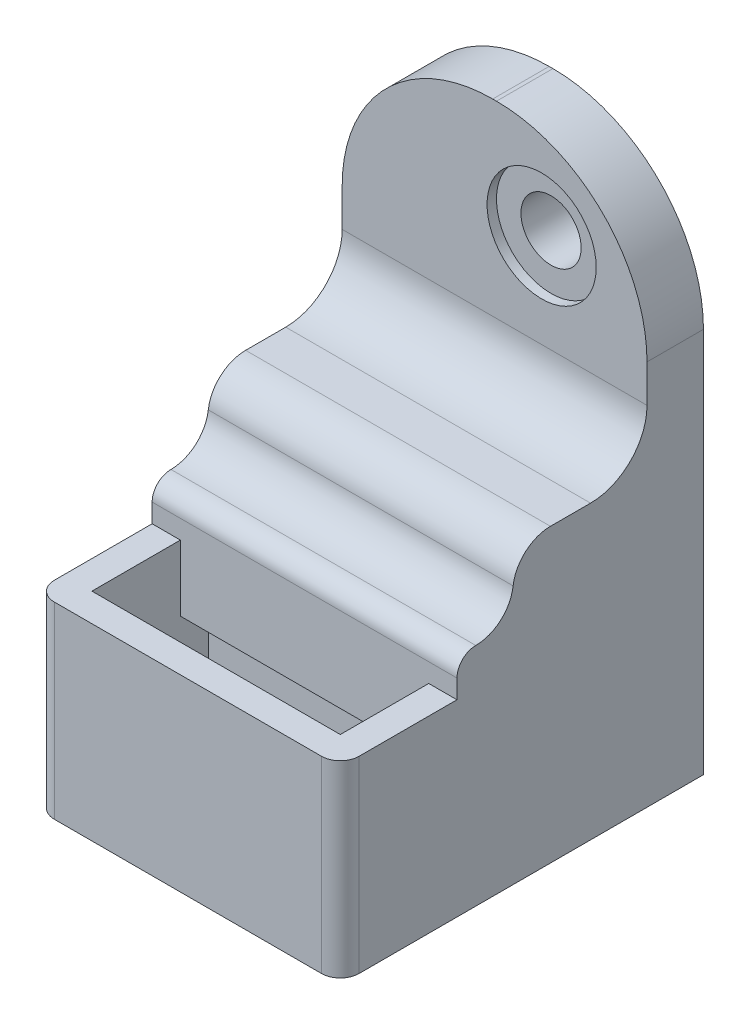
SolidWorks part; units mm, degrees
ref_plane "Alzado" through (0, 0, 0) normal (0, 0, 1) x (1, 0, 0)
ref_plane "Planta" through (0, 0, 0) normal (0, 1, 0) x (1, 0, 0)
ref_plane "Vista lateral" through (0, 0, 0) normal (1, 0, 0) x (0, 0, -1)
sketch "Croquis2" plane through (0, 0, 0) normal (0, 1, 0) x (1, 0, 0)
  line L0 (-1.5, 1.5) -> (14.7, 1.5)
  line L1 (0, 0) -> (13.2, 0)
  line L2 (0, 0) -> (0, -6.2)
  line L3 (0, -6.2) -> (13.2, -6.2)
  line L4 (13.2, 0) -> (13.2, -6.2)
  line L5 (14.7, 1.5) -> (14.7, -7.7)
  line L6 (-1.5, -7.7) -> (14.7, -7.7)
  line L7 (-1.5, 1.5) -> (-1.5, -7.7)
  dimension "D1" = 13.2
  dimension "D2" = 6.2
  dimension "D3" = 1.5
extrude "Saliente-Extruir1" add sketch "Croquis2" along normal blind 6.5
sketch "Croquis3" plane through (0, 0, -1.5) normal (0, 0, -1) x (-1, 0, 0)
  line L1 (1.5, 0) -> (-14.7, 0)
  line L2 (1.5, 0) -> (1.5, 12)
  line L3 (1.5, 12) -> (-14.7, 12)
  line L4 (-14.7, 0) -> (-14.7, 12)
  line L6 (-14.7, 0) -> (1.5, 0) construction
  line L8 (-14.7, 6.5) -> (-14.7, 0) construction
  line L9 (1.5, 6.5) -> (1.5, 0) construction
  dimension "D1" = 12
extrude "Saliente-Extruir2" add sketch "Croquis3" along normal blind 2
sketch "Croquis4" plane through (0, 0, -3.5) normal (0, 0, -1) x (-1, 0, 0)
  line L10 (1.5, 0) -> (1.5, 12) construction
  line L11 (1.5, 12) -> (-14.7, 12) construction
  line L12 (-14.7, 12) -> (-14.7, 0) construction
  line L13 (1.5, 0) -> (1.5, 12)
  line L14 (1.5, 12) -> (-14.7, 12)
  line L15 (-14.7, 12) -> (-14.7, 0)
  line L16 (-0.3, 0) -> (-0.3, 10)
  line L17 (-14.7, 0) -> (1.5, 0) construction
  line L18 (-0.3, 10) -> (-12.9, 10)
  line L19 (-12.9, 10) -> (-12.9, 0)
  line L20 (1.5, 0) -> (-0.3, 0)
  line L21 (-12.9, 0) -> (-14.7, 0)
  dimension "D1" = 2
  dimension "D2" = 1.8
  dimension "D3" = 1.8
extrude "Saliente-Extruir3" add sketch "Croquis4" along normal blind 8.1
sketch "Croquis5" plane through (0, 12, 0) normal (0, 1, 0) x (1, 0, 0)
  line L0 (-1.5, 11.6) -> (-1.5, 1.5) construction
  line L1 (14.7, 11.6) -> (-1.5, 11.6)
  line L2 (14.7, 11.6) -> (14.7, 8.6)
  line L3 (14.7, 8.6) -> (-1.5, 8.6)
  line L4 (-1.5, 11.6) -> (-1.5, 8.6)
  dimension "D1" = 3
extrude "Saliente-Extruir4" add sketch "Croquis5" along normal blind 13
sketch "Croquis6" plane through (0, 0, -8.6) normal (0, 0, 1) x (1, 0, 0)
  line L0 (14.7, 25) -> (14.7, 12) construction
  line L1 (-1.5, 25) -> (14.7, 25) construction
  circle A0 centre (9.1, 20) radius 1.6
  dimension "D1" = 3.2
  dimension "D2" = 5.6
  dimension "D3" = 5
extrude "Cortar-Extruir1" cut sketch "Croquis6" against normal up to surface (3 mm away) up to face at (6.6, 8.75, -11.6)
sketch "Croquis7" plane through (0, 0, -1.5) normal (0, 0, 1) x (1, 0, 0)
  line L0 (-1.5, 6.5) -> (-1.5, 12) construction
  line L1 (14.7, 6.5) -> (-1.5, 6.5)
  line L2 (14.7, 6.5) -> (14.7, 8.5)
  line L3 (14.7, 8.5) -> (-1.5, 8.5)
  line L4 (-1.5, 6.5) -> (-1.5, 8.5)
  dimension "D1" = 2
extrude "Saliente-Extruir5" add sketch "Croquis7" along normal blind 3
sketch "Croquis8" plane through (0, 0, -8.6) normal (0, 0, 1) x (1, 0, 0)
  circle A0 centre (9.1, 20) radius 2.9
  dimension "D1" = 5.8
extrude "Cortar-Extruir2" cut sketch "Croquis8" against normal blind 0.5
fillet "Redondeo1" radius 1 2 edges at (-1.5, 3.25, 7.7) (14.7, 3.25, 7.7)
fillet "Redondeo2" radius 1 1 edges at (6.6, 8.5, 1.5)
fillet "Redondeo3" radius 2 1 edges at (6.6, 8.5, -1.5)
fillet "Redondeo4" radius 2 1 edges at (6.6, 12, -1.5)
fillet "Redondeo5" radius 3 1 edges at (6.6, 12, -8.6)
fillet "Redondeo6" radius 8 2 edges at (14.7, 25, -10.1) (-1.5, 25, -10.1)
sketch "Croquis9" plane through (0, 0, 0) normal (0, -1, 0) x (1, 0, 0)
  line L0 (0, 0) -> (0, 6.2) construction
  line L1 (0, 6.2) -> (13.2, 6.2) construction
  line L2 (13.2, 6.2) -> (13.2, 0) construction
  line L3 (13.2, 0) -> (0, 0) construction
  line L4 (0, 0) -> (0, 6.2)
  line L5 (0, 6.2) -> (13.2, 6.2)
  line L6 (13.2, 6.2) -> (13.2, 0)
  line L7 (13.2, 0) -> (0, 0)
  line L8 (13.7, 7.7) -> (-0.5, 7.7)
  line L9 (-1.5, 6.7) -> (-1.5, -11.6)
  line L10 (-1.5, -11.6) -> (0.3, -11.6)
  line L11 (0.3, -11.6) -> (0.3, -3.5)
  line L12 (0.3, -3.5) -> (12.9, -3.5)
  line L13 (12.9, -3.5) -> (12.9, -11.6)
  line L14 (12.9, -11.6) -> (14.7, -11.6)
  line L15 (14.7, -11.6) -> (14.7, 6.7)
  line L16 (13.7, 7.7) -> (-0.5, 7.7)
  line L17 (-1.5, 6.7) -> (-1.5, -11.6)
  line L18 (-1.5, -11.6) -> (0.3, -11.6)
  line L19 (0.3, -11.6) -> (0.3, -3.5)
  line L20 (0.3, -3.5) -> (12.9, -3.5)
  line L21 (12.9, -3.5) -> (12.9, -11.6)
  line L22 (12.9, -11.6) -> (14.7, -11.6)
  line L23 (14.7, -11.6) -> (14.7, 6.7)
  arc A2 (-0.5, 7.7) -> (-1.5, 6.7) centre (-0.5, 6.7) ccw
  arc A3 (14.7, 6.7) -> (13.7, 7.7) centre (13.7, 6.7) ccw
  arc A4 (-0.5, 7.7) -> (-1.5, 6.7) centre (-0.5, 6.7) ccw
  arc A5 (14.7, 6.7) -> (13.7, 7.7) centre (13.7, 6.7) ccw
  dimension "D1" = 0
extrude "Saliente-Extruir6" add sketch "Croquis9" along normal blind 3.5
sketch "Croquis10" plane through (0, 6.5, 0) normal (0, -1, 0) x (1, 0, 0)
  line L4 (0, 1.5) -> (0, 0)
  line L5 (0, 0) -> (13.2, 0)
  line L6 (13.2, 0) -> (13.2, 1.5)
  line L7 (13.2, 1.5) -> (0, 1.5)
  line L8 (0, 1.5) -> (0, 0)
  line L9 (0, 0) -> (13.2, 0)
  line L10 (13.2, 0) -> (13.2, 1.5)
  line L11 (13.2, 1.5) -> (0, 1.5)
  dimension "D1" = 0
extrude "Saliente-Extruir7" add sketch "Croquis10" along normal blind 3.5
